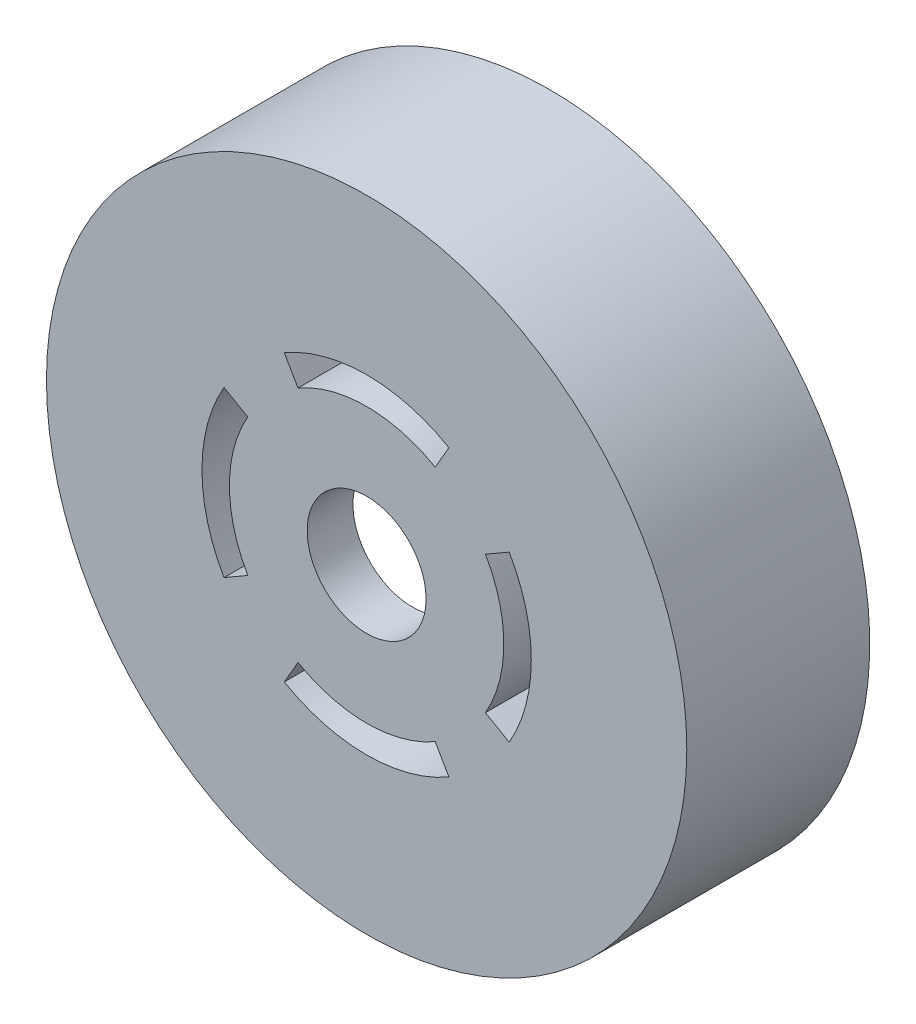
SolidWorks part; units mm, degrees
ref_plane "前视基准面" through (0, 0, 0) normal (0, 0, 1) x (1, 0, 0)
ref_plane "上视基准面" through (0, 0, 0) normal (0, 1, 0) x (1, 0, 0)
ref_plane "右视基准面" through (0, 0, 0) normal (1, 0, 0) x (0, 0, -1)
other "Configuration Table"
sketch "草图2" plane through (0, 0, 0) normal (0, 0, 1) x (1, 0, 0)
  circle A0 centre (0, 0) radius 35
  circle A1 centre (0, 0) radius 6.5
  dimension "D1" = 70
  dimension "D2" = 13
extrude "凸台-拉伸1" add sketch "草图2" along normal blind 5
sketch "草图3" plane through (0, 0, 0) normal (0, 0, -1) x (-1, 0, 0)
  circle A0 centre (0, 0) radius 30.05
  circle A1 centre (0, 0) radius 35
  dimension "D1" = 60.1
extrude "凸台-拉伸2" add sketch "草图3" along normal blind 15
sketch "草图4" plane through (0, 0, -15) normal (0, 0, -1) x (-1, 0, 0)
  line L0 (0, 0) -> (0, 32.5)
  line L1 (0, 0) -> (32.5, 0)
  line L2 (0, 0) -> (0, -32.5)
  line L3 (0, 0) -> (-32.5, 0)
  circle A0 centre (0, 32.5) radius 1.55
  circle A1 centre (32.5, 0) radius 1.55
  circle A2 centre (0, -32.5) radius 1.55
  circle A3 centre (-32.5, 0) radius 1.55
  point P9 (0, 0)
  point P17 (0, 0)
  dimension "D2" = 4
  dimension "D1" = 4
extrude "切除-拉伸1" cut sketch "草图4" against normal blind 10 contours A0 | A1 | A2 | A3 region at (1.065, 33.565, -15) region at (-32.5, 1.5062, -15) region at (-1.065, -31.435, -15) region at (34.0062, 0, -15)
fillet "圆角1" radius 1 1 edges at (-30.05, 0, -15)
sketch "草图5" plane through (0, 0, 0) normal (0, 0, -1) x (-1, 0, 0)
  line L0 (12.9904, -7.5) -> (15.5885, -9)
  line L1 (12.9904, 7.5) -> (15.5885, 9)
  line L2 (-7.5, 12.9904) -> (-9, 15.5885)
  line L3 (7.5, 12.9904) -> (9, 15.5885)
  line L4 (-7.5, -12.9904) -> (-9, -15.5885)
  line L5 (7.5, -12.9904) -> (9, -15.5885)
  line L6 (-12.9904, 7.5) -> (-15.5885, 9)
  line L7 (-12.9904, -7.5) -> (-15.5885, -9)
  arc A1 (7.5, 12.9904) -> (-7.5, 12.9904) centre (0, 0) ccw
  arc A2 (9, 15.5885) -> (-9, 15.5885) centre (0, 0) ccw
  arc A3 (12.9904, -7.5) -> (12.9904, 7.5) centre (0, 0) ccw
  arc A4 (15.5885, -9) -> (15.5885, 9) centre (0, 0) ccw
  arc A5 (-7.5, -12.9904) -> (7.5, -12.9904) centre (0, 0) ccw
  arc A6 (-9, -15.5885) -> (9, -15.5885) centre (0, 0) ccw
  arc A7 (-12.9904, 7.5) -> (-12.9904, -7.5) centre (0, 0) ccw
  arc A8 (-15.5885, 9) -> (-15.5885, -9) centre (0, 0) ccw
  point P21 (0, 0)
  dimension "D1" = 4
extrude "切除-拉伸2" cut sketch "草图5" against normal through all
